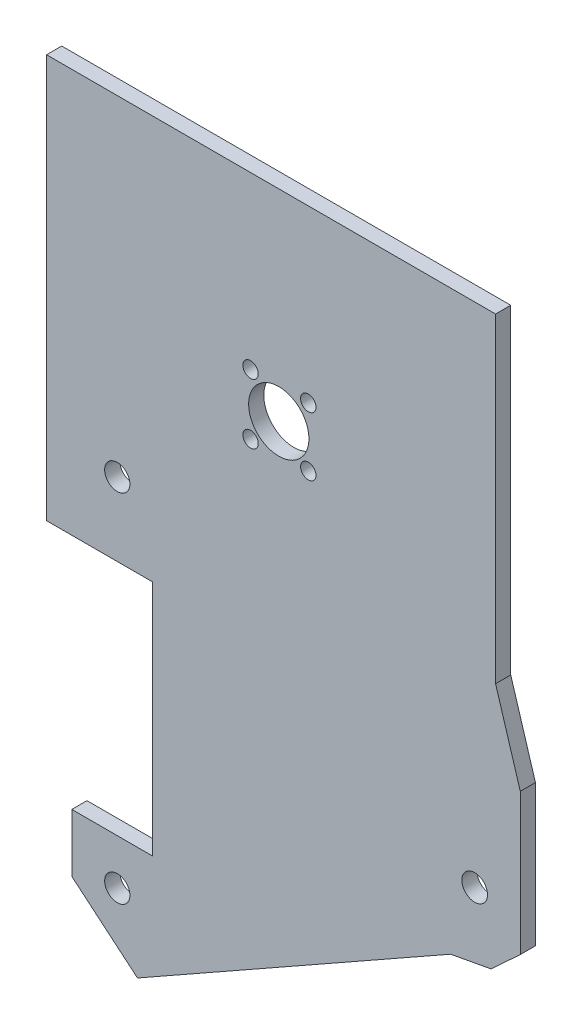
SolidWorks part; units mm, degrees
ref_plane "Front Plane" through (0, 0, 0) normal (0, 0, 1) x (1, 0, 0)
ref_plane "Top Plane" through (0, 0, 0) normal (0, 1, 0) x (1, 0, 0)
ref_plane "Right Plane" through (0, 0, 0) normal (1, 0, 0) x (0, 0, -1)
sketch "Sketch1" plane through (0, 0, 0) normal (0, 0, 1) x (1, 0, 0)
  line L0 (0, 0) -> (88.9, 0)
  line L1 (88.9, 0) -> (88.9, -3.5)
  line L2 (88.9, -3.5) -> (93.7917, -19.5)
  line L3 (93.7917, -19.5) -> (93.7917, -47.5)
  line L4 (0, 0) -> (0, -20)
  line L5 (0, -20) -> (21, -20)
  line L6 (21, -20) -> (21, -67)
  line L7 (21, -67) -> (5, -67)
  line L8 (5, -67) -> (5, -78.5)
  line L9 (5, -78.5) -> (18, -89.4083)
  line L10 (18, -89.4083) -> (80, -54.3304)
  line L11 (80, -54.3304) -> (88, -52.8477)
  line L12 (88, -52.8477) -> (93.7917, -47.5)
  dimension "D1" = 88.9
  dimension "D2" = 3.5
  dimension "D3" = 163
  dimension "D4" = 16
  dimension "D5" = 28
  dimension "D6" = 20
  dimension "D7" = 21
  dimension "D8" = 47
  dimension "D9" = 16
  dimension "D10" = 11.5
  dimension "D11" = 130
  dimension "D12" = 13
  dimension "D13" = 110.5
  dimension "D14" = 62
  dimension "D15" = 8
  dimension "D16" = 161
extrude "Boss-Extrude1" add sketch "Sketch1" along normal blind 3
sketch "Sketch2" plane through (0, 0, 0) normal (0, 1, 0) x (1, 0, 0)
  line L0 (45.8978, 14) -> (40.3978, 14) construction
  line L1 (0, -3) -> (88.9, -3)
  line L2 (0, -3) -> (0, 54)
  line L3 (0, 54) -> (88.9, 54)
  line L4 (88.9, -3) -> (88.9, 54)
  circle A0 centre (40.3978, 8.5) radius 1.5
  circle A1 centre (40.3978, 20) radius 1.5
  circle A2 centre (51.8978, 8.5) radius 1.5
  circle A3 centre (51.8978, 20) radius 1.5
  ellipse E0 centre (45.8978, 14) end of major axis (45.8978, 8) minor radius 5.5
  dimension "D9" = 3
  dimension "D10" = 3
  dimension "D11" = 3
  dimension "D12" = 3
  dimension "D1" = 88.9
  dimension "D2" = 57
  dimension "D3" = 45.8978
  dimension "D4" = 5.5
  dimension "D5" = 11.5
  dimension "D6" = 23
  dimension "D7" = 11.5
  dimension "D8" = 17
  dimension "D13" = 12
  dimension "D14" = 11
extrude "Boss-Extrude2" add sketch "Sketch2" along normal blind 3
ref_plane "Plane1" through (85.9, 0, 0) normal (1, 0, 0) x (0, 0, -1)
sketch "Sketch3" plane through (85.9, 0, 0) normal (1, 0, 0) x (0, 0, -1)
  line L0 (11.5, 0) -> (0, 0)
  line L1 (0, 0) -> (54, 0) construction
  line L2 (0, 0) -> (0, -11.5)
  line L3 (0, -19.5) -> (0, -3.5) construction
  line L4 (0, -11.5) -> (11.5, 0)
  dimension "D1" = 11.5
  dimension "D2" = 11.5
extrude "Boss-Extrude3" add sketch "Sketch3" against normal blind 84.5
sketch "Sketch4" plane through (0, 0, 0) normal (0, 0, -1) x (-1, 0, 0)
  line L0 (-1.4, -11.5) -> (-85.9, -11.5) construction
  line L1 (-81.4, -11.5) -> (-6.4, -11.5)
  line L2 (-81.4, -11.5) -> (-81.4, 0)
  line L3 (-81.4, 0) -> (-6.4, 0)
  line L4 (-6.4, -11.5) -> (-6.4, 0)
  line L5 (-50.8976, 0) -> (-85.9, 0) construction
  line L6 (-85.9, 13.7659) -> (-85.9, -13.7659) construction
  dimension "D1" = 75
  dimension "D2" = 4.5
extrude "Cut-Extrude2" cut sketch "Sketch4" along normal blind 84.5
sketch "Sketch6" plane through (0, 0, 3) normal (0, 0, 1) x (1, 0, 0)
  line L0 (0, 3) -> (0, -20) construction
  line L1 (0, 3) -> (88.9, 3) construction
  circle A0 centre (14, -76) radius 2.5
  circle A1 centre (84.763, -40.5) radius 2.54
  circle A2 centre (14, -5.5) radius 2.5
  dimension "D1" = 5
  dimension "D2" = 5
  dimension "D3" = 5.08
  dimension "D4" = 14
  dimension "D5" = 8.5
  dimension "D6" = 70.5
  dimension "D7" = 14
  dimension "D8" = 43.5
  dimension "D9" = 70.763
extrude "Cut-Extrude3" cut sketch "Sketch6" against normal blind 84.5
sketch "Sketch7" plane through (0, 0, 0) normal (0, -1, 0) x (1, 0, 0)
  line L1 (88.9, -54) -> (0, -54)
  line L2 (88.9, -54) -> (88.9, 0)
  line L3 (88.9, 0) -> (0, 0)
  line L4 (0, -54) -> (0, 0)
extrude "Cut-Extrude4" cut sketch "Sketch7" against normal through all both and the other way through all
sketch "Sketch8" plane through (0, 0, 0) normal (0, 0, -1) x (-1, 0, 0)
  line L0 (-88.9, 3) -> (0, 3) construction
  line L1 (-88.9, 3) -> (0, 3)
  line L2 (-88.9, 3) -> (-88.9, 59.896)
  line L3 (-88.9, 59.896) -> (0, 59.896)
  line L4 (0, 3) -> (0, 59.896)
  line L5 (-45.974, 20.018) -> (-40.005, 20.018) construction
  circle A0 centre (-45.974, 20.018) radius 5.969
  circle A1 centre (-40.386, 26.114) radius 1.524
  circle A2 centre (-40.386, 14.176) radius 1.524
  circle A3 centre (-51.816, 26.114) radius 1.524
  circle A4 centre (-51.816, 14.43) radius 1.524
  dimension "D8" = 11.938
  dimension "D9" = 3.048
  dimension "D10" = 3.048
  dimension "D11" = 3.048
  dimension "D12" = 3.048
  dimension "D1" = 56.896
  dimension "D2" = 88.9
  dimension "D3" = 23.114
  dimension "D4" = 11.43
  dimension "D5" = 17.018
  dimension "D6" = 11.938
  dimension "D7" = 5.588
  dimension "D13" = 45.974
  dimension "D14" = 11.43
extrude "Boss-Extrude4" add sketch "Sketch8" against normal up to surface (3 mm away) up to face at (16.5, -76, 3)
